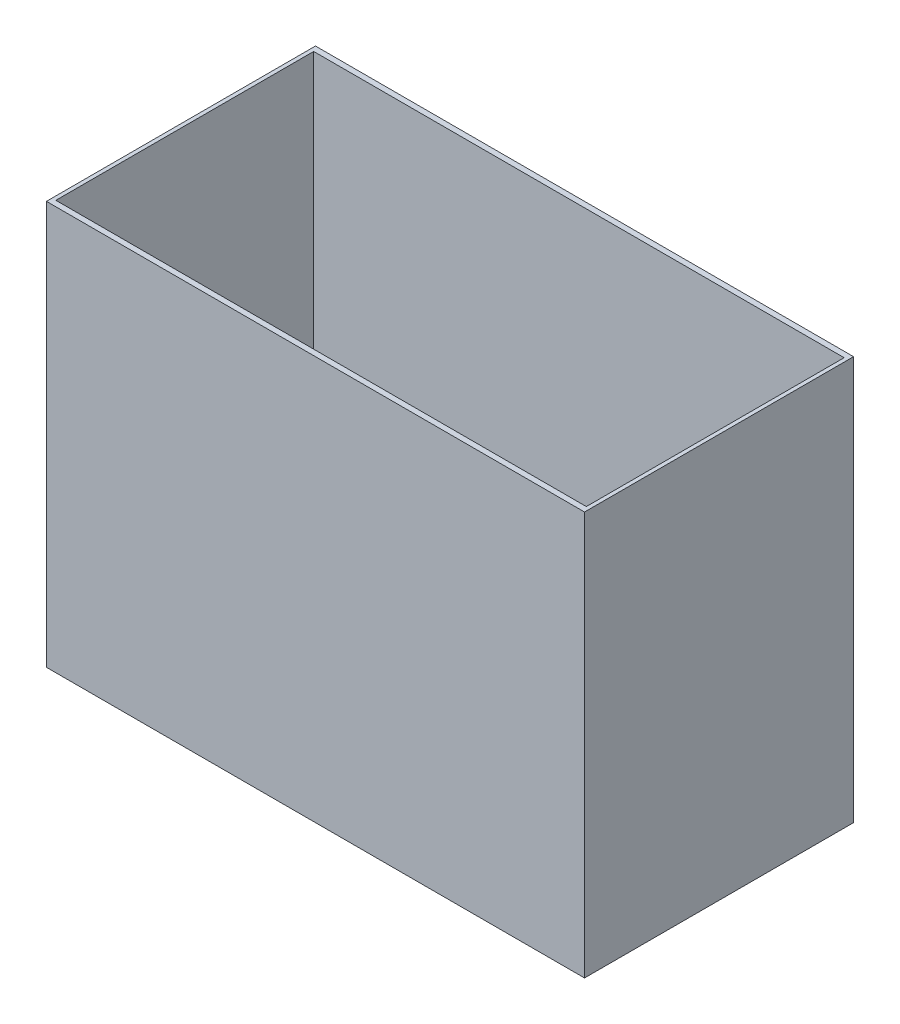
SolidWorks part; units mm, degrees
ref_plane "Front Plane" through (0, 0, 0) normal (0, 0, 1) x (1, 0, 0)
ref_plane "Top Plane" through (0, 0, 0) normal (0, 1, 0) x (1, 0, 0)
ref_plane "Right Plane" through (0, 0, 0) normal (1, 0, 0) x (0, 0, -1)
other "Bounding Box"
ref_plane "Default Plane" through (-292.1, 0, -139.7) normal (0, 1, 0) x (1, 0, 0)
sketch "Sketch1" plane through (0, 0, 0) normal (0, 1, 0) x (1, 0, 0)
  line L0 (-292.1, 0) -> (292.1, 0) construction
  line L1 (-292.1, 139.7) -> (292.1, 139.7)
  line L2 (-292.1, 139.7) -> (-292.1, -139.7)
  line L3 (-292.1, -139.7) -> (292.1, -139.7)
  line L4 (292.1, 139.7) -> (292.1, -139.7)
  line L5 (0, 139.7) -> (0, -139.7) construction
  point P8 (0, 0)
  dimension "D1" = 584.2
  dimension "D2" = 279.4
extrude "Boss-Extrude1" add sketch "Sketch1" along normal blind 6.35
sketch "Sketch2" plane through (0, 6.35, 0) normal (0, 1, 0) x (1, 0, 0)
  line L0 (-245.9259, -63.5) -> (-55.3589, -63.5) construction
  line L1 (-241.3, -120.6497) -> (-152.4, -120.6497)
  line L2 (-241.3, -120.6497) -> (-241.3, -101.5997)
  line L3 (-241.3, -101.5997) -> (-152.4, -101.5997)
  line L4 (-152.4, -120.6497) -> (-152.4, -101.5997)
  line L5 (-241.3, -120.6497) -> (-152.4, -101.5997) construction
  line L6 (-241.3, -101.5997) -> (-152.4, -120.6497) construction
  line L7 (-292.1, 139.7) -> (-292.1, -139.7) construction
  line L8 (-292.1, 0) -> (292.1, 0) construction
  line L9 (292.1, -139.7) -> (292.1, 139.7) construction
  line L10 (0, 0) -> (0, 121.6784) construction
  line L11 (241.3, -101.5997) -> (152.4, -120.6497) construction
  line L12 (241.3, -120.6497) -> (152.4, -101.5997) construction
  line L13 (152.4, -120.6497) -> (152.4, -101.5997)
  line L14 (241.3, -101.5997) -> (152.4, -101.5997)
  line L15 (241.3, -120.6497) -> (241.3, -101.5997)
  line L16 (241.3, -120.6497) -> (152.4, -120.6497)
  point P0 (-196.85, -111.1247)
  point P17 (196.85, -111.1247)
  dimension "D1" = 19.05
  dimension "D2" = 88.9
  dimension "D3" = 38.0997
  dimension "D4" = 50.8
  dimension "D5" = 63.5
extrude "Boss-Extrude2" [suppressed] add sketch "Sketch2" along normal blind 304.8 separate body contours L2 L1 L4 L3
pattern_linear "LPattern1" [suppressed] count 2 spacing 304.8 of bodies 101
pattern_linear "LPattern2" [suppressed] count 2 spacing 215.9 of bodies 101
sketch "Sketch3" plane through (0, 0, 0) normal (0, 1, 0) x (1, 0, 0)
  line L1 (-304.8, -152.4) -> (304.8, -152.4)
  line L2 (-304.8, -152.4) -> (-304.8, 152.4)
  line L3 (-304.8, 152.4) -> (304.8, 152.4)
  line L4 (304.8, -152.4) -> (304.8, 152.4)
  line L5 (-304.8, -152.4) -> (304.8, 152.4) construction
  line L6 (-304.8, 152.4) -> (304.8, -152.4) construction
  line L7 (-300.482, -146.05) -> (300.482, -146.05)
  line L8 (-300.482, -146.05) -> (-300.482, 146.05)
  line L9 (-300.482, 146.05) -> (300.482, 146.05)
  line L10 (300.482, -146.05) -> (300.482, 146.05)
  line L11 (-300.482, -146.05) -> (300.482, 146.05) construction
  line L12 (-300.482, 146.05) -> (300.482, -146.05) construction
  point P0 (0, 0)
  point P6 (0, 0)
  dimension "D1" = 609.6
  dimension "D2" = 304.8
  dimension "D3" = 292.1
  dimension "D4" = 600.964
extrude "Boss-Extrude3" add sketch "Sketch3" along normal blind 457.2 separate body
sketch "Sketch4" plane through (0, 6.35, 0) normal (0, 1, 0) x (1, 0, 0)
  line L0 (292.1, -139.7) -> (292.1, 139.7) construction
  line L1 (238.8561, 120.65) -> (261.8611, 120.65) construction
  line L2 (273.05, 95.4723) -> (273.05, 121.6668) construction
  line L3 (292.1, 139.7) -> (-292.1, 139.7) construction
  circle A3 centre (252.0119, 99.6119) radius 21.0381
  dimension "D1" = 42.0762
  dimension "D2" = 19.05
  dimension "D3" = 19.05
extrude "Cut-Extrude1" cut sketch "Sketch4" against normal through all
sketch "Sketch7" plane through (0, 6.35, 0) normal (0, 1, 0) x (1, 0, 0)
  line L0 (292.1, 0) -> (49.4912, 0) construction
  line L1 (292.1, -139.7) -> (292.1, 139.7) construction
  circle A0 centre (190.5, 0) radius 4 construction
  circle A1 centre (190.5, 0) radius 2.7781
  dimension "D1" = 8
  dimension "D2" = 5.5562
  dimension "D3" = 101.6
extrude "Cut-Extrude3" [suppressed] cut sketch "Sketch7" against normal through all
sketch "Sketch8" [suppressed] plane through (0, 6.35, 0) normal (0, 1, 0) x (1, 0, 0)
  circle A0 centre (94.9, -12.8415) radius 1.9844 construction
  circle A1 centre (146.1, -12.8415) radius 1.9844 construction
  circle A2 centre (146.1, 12.8415) radius 1.9844 construction
  circle A3 centre (94.9, 12.8415) radius 1.9844 construction
  circle A4 centre (94.9, -12.8415) radius 1.9844
  circle A5 centre (146.1, -12.8415) radius 1.9844
  circle A6 centre (146.1, 12.8415) radius 1.9844
  circle A7 centre (94.9, 12.8415) radius 1.9844
extrude "Cut-Extrude4" [suppressed] cut sketch "Sketch8" against normal through all
sketch "Sketch9" plane through (0, 0, 0) normal (0, -1, 0) x (1, 0, 0)
  circle A1 centre (190.5, 0) radius 6.35
  circle A2 centre (146.1, 12.8415) radius 6.35
  circle A3 centre (94.9, 12.8415) radius 6.35
  circle A4 centre (94.9, -12.8415) radius 6.35
  circle A5 centre (146.1, -12.8415) radius 6.35
sketch "Sketch11" plane through (0, 0, 0) normal (0, -1, 0) x (1, 0, 0)
  line L0 (-292.1, 139.7) -> (292.1, 139.7) construction
  line L1 (215.9, 139.7) -> (165.1, 139.7)
  line L2 (215.9, 139.7) -> (215.9, 136.525)
  line L3 (215.9, 136.525) -> (165.1, 136.525)
  line L4 (165.1, 139.7) -> (165.1, 136.525)
  line L5 (292.1, 139.7) -> (292.1, -139.7) construction
  dimension "D1" = 3.175
  dimension "D2" = 50.8
  dimension "D3" = 76.2
extrude "Cut-Extrude6" cut sketch "Sketch11" against normal through all
mirror "Mirror2" about plane through (0, 0, 0) normal (0, 0, 1) of "Cut-Extrude1", "Cut-Extrude6"
sketch "Sketch12" plane through (0, 6.35, 0) normal (0, 1, 0) x (1, 0, 0)
  line L0 (292.1, -17.78) -> (285.75, -17.78) construction
  line L1 (292.1, -43.18) -> (285.75, -43.18) construction
  line L2 (285.75, -43.18) -> (285.75, -17.78) construction
  line L3 (292.1, -78.74) -> (285.75, -78.74) construction
  line L4 (292.1, -104.14) -> (285.75, -104.14) construction
  line L5 (285.75, -78.74) -> (285.75, -104.14) construction
  line L6 (292.1, -17.78) -> (285.75, -17.78)
  line L7 (292.1, -43.18) -> (285.75, -43.18)
  line L8 (285.75, -43.18) -> (285.75, -17.78)
  line L9 (292.1, -78.74) -> (285.75, -78.74)
  line L10 (292.1, -104.14) -> (285.75, -104.14)
  line L11 (285.75, -78.74) -> (285.75, -104.14)
  line L12 (292.1, 0) -> (257.5404, 0) construction
  line L13 (285.75, 78.74) -> (285.75, 104.14)
  line L14 (292.1, 104.14) -> (285.75, 104.14)
  line L15 (292.1, 78.74) -> (285.75, 78.74)
  line L16 (285.75, 43.18) -> (285.75, 17.78)
  line L17 (292.1, 43.18) -> (285.75, 43.18)
  line L18 (292.1, 17.78) -> (285.75, 17.78)
  line L19 (292.1, -139.7) -> (292.1, 139.7) construction
  line L20 (292.1, -104.14) -> (292.1, -78.74)
  line L21 (292.1, -43.18) -> (292.1, -17.78)
  line L22 (292.1, 17.78) -> (292.1, 43.18)
  line L23 (292.1, 78.74) -> (292.1, 104.14)
extrude "Cut-Extrude7" cut sketch "Sketch12" against normal through all
sketch "Sketch13" plane through (0, 6.35, 0) normal (0, 1, 0) x (1, 0, 0)
  line L0 (252.0119, -99.6119) -> (133.5003, -46.1866) construction
  line L1 (210.6176, 12.194) -> (133.5003, -46.1866) construction
  line L2 (252.0119, 99.6119) -> (210.6176, 12.194) construction
  line L3 (257.6906, -66.7163) -> (23.4514, -66.7163) construction
  circle A0 centre (252.0119, -99.6119) radius 21.0381 construction
  circle A1 centre (252.0119, -99.6119) radius 21.0381 construction
  circle A2 centre (133.5003, -46.1866) radius 21.0381
  circle A3 centre (210.6176, 12.194) radius 21.0381
  circle A4 centre (252.0119, 99.6119) radius 21.0381 construction
  circle A5 centre (252.0119, 99.6119) radius 21.0381 construction
  circle A6 centre (210.6176, 12.194) radius 55.7022 construction
  point P9 (135.4762, -42.0037)
  point P11 (0, 0)
  point P15 (133.5003, -46.1866)
  dimension "D1" = 129.9972
  dimension "D3" = 111.4044
  dimension "D2" = 96.7232
  dimension "D4" = 96.7232
extrude "Cut-Extrude8" cut sketch "Sketch13" against normal through all
sketch "Sketch14" plane through (0, 6.35, 0) normal (0, 1, 0) x (1, 0, 0)
  circle A1 centre (45.3035, 4.219) radius 4.7113 construction
  circle A2 centre (45.3035, 4.219) radius 2.7781
  dimension "D1" = 5.5562
extrude "Cut-Extrude9" cut sketch "Sketch14" against normal through all
sketch "Sketch15" plane through (0, 0, 0) normal (0, -1, 0) x (1, 0, 0)
  line L0 (88.9, -38.1) -> (88.9, -57.15) construction
  line L1 (88.9, -57.15) -> (95.25, -57.15) construction
  line L2 (95.25, -57.15) -> (95.25, -38.1) construction
  line L3 (95.25, -38.1) -> (88.9, -38.1) construction
  line L4 (88.9, 57.15) -> (88.9, 31.75) construction
  line L5 (88.9, 31.75) -> (95.25, 31.75) construction
  line L6 (95.25, 31.75) -> (95.25, 57.15) construction
  line L7 (95.25, 57.15) -> (88.9, 57.15) construction
  line L8 (88.9, -38.1) -> (88.9, -57.15) construction
  line L9 (88.9, -57.15) -> (95.25, -57.15) construction
  line L10 (95.25, -57.15) -> (95.25, -38.1) construction
  line L11 (95.25, -38.1) -> (88.9, -38.1) construction
  line L12 (88.9, 57.15) -> (88.9, 31.75) construction
  line L13 (88.9, 31.75) -> (95.25, 31.75) construction
  line L14 (95.25, 31.75) -> (95.25, 57.15) construction
  line L15 (95.25, 57.15) -> (88.9, 57.15) construction
  line L16 (88.773, -37.973) -> (88.773, -57.277)
  line L17 (88.773, -57.277) -> (95.377, -57.277)
  line L18 (95.377, -57.277) -> (95.377, -37.973)
  line L19 (95.377, -37.973) -> (88.773, -37.973)
  line L20 (88.773, 57.277) -> (88.773, 31.623)
  line L21 (88.773, 31.623) -> (95.377, 31.623)
  line L22 (95.377, 31.623) -> (95.377, 57.277)
  line L23 (95.377, 57.277) -> (88.773, 57.277)
  dimension "D1" = 0.127
  dimension "D2" = 0.127
extrude "Cut-Extrude10" cut sketch "Sketch15" against normal through all
sketch "Sketch16" plane through (0, 0, 0) normal (0, -1, 0) x (1, 0, 0)
  line L0 (-63.5, -66.675) -> (-63.5, -53.975) construction
  line L1 (-63.5, -53.975) -> (-38.1, -53.975) construction
  line L2 (-38.1, -66.675) -> (-38.1, -53.975) construction
  line L3 (-63.5, -66.675) -> (-38.1, -66.675) construction
  line L4 (-215.9, -66.675) -> (-215.9, -53.975) construction
  line L5 (-241.3, -53.975) -> (-215.9, -53.975) construction
  line L6 (-241.3, -66.675) -> (-241.3, -53.975) construction
  line L7 (-241.3, -66.675) -> (-215.9, -66.675) construction
  line L8 (-63.5, -66.675) -> (-63.5, -53.975)
  line L9 (-63.5, -53.975) -> (-38.1, -53.975)
  line L10 (-38.1, -66.675) -> (-38.1, -53.975)
  line L11 (-63.5, -66.675) -> (-38.1, -66.675)
  line L12 (-215.9, -66.675) -> (-215.9, -53.975)
  line L13 (-241.3, -53.975) -> (-215.9, -53.975)
  line L14 (-241.3, -66.675) -> (-241.3, -53.975)
  line L15 (-241.3, -66.675) -> (-215.9, -66.675)
  line L16 (-292.1, 0) -> (-84.0789, 0) construction
  line L17 (-292.1, -139.7) -> (-292.1, 139.7) construction
  line L18 (-241.3, 66.675) -> (-215.9, 66.675)
  line L19 (-241.3, 66.675) -> (-241.3, 53.975)
  line L20 (-241.3, 53.975) -> (-215.9, 53.975)
  line L21 (-215.9, 66.675) -> (-215.9, 53.975)
  line L22 (-63.5, 66.675) -> (-38.1, 66.675)
  line L23 (-38.1, 66.675) -> (-38.1, 53.975)
  line L24 (-63.5, 53.975) -> (-38.1, 53.975)
  line L25 (-63.5, 66.675) -> (-63.5, 53.975)
extrude "Cut-Extrude11" cut sketch "Sketch16" against normal through all
